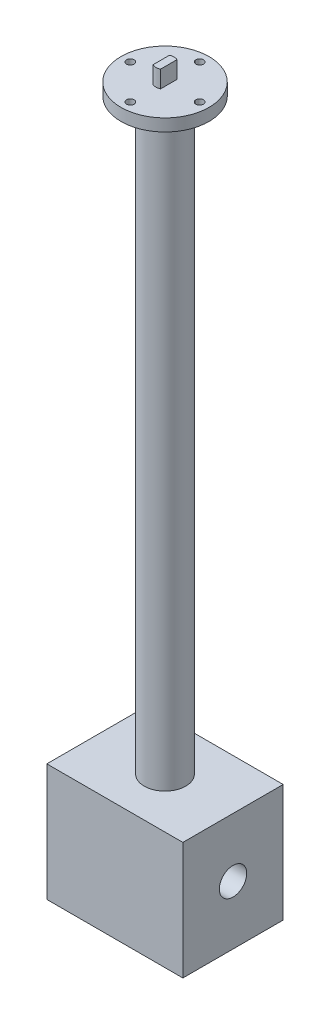
SolidWorks part; units mm, degrees
ref_plane "Front Plane" through (0, 0, 0) normal (0, 0, 1) x (1, 0, 0)
ref_plane "Top Plane" through (0, 0, 0) normal (0, 1, 0) x (1, 0, 0)
ref_plane "Right Plane" through (0, 0, 0) normal (1, 0, 0) x (0, 0, -1)
sketch "Sketch1" plane through (0, 0, 0) normal (0, 1, 0) x (1, 0, 0)
  circle A0 centre (0, 0) radius 22.86
  dimension "D1" = 45.72
extrude "Boss-Extrude1" add sketch "Sketch1" along normal blind 6.35
sketch "Sketch2" plane through (0, 6.35, 0) normal (0, 1, 0) x (1, 0, 0)
  line L0 (1.9685, 4.2668) -> (1.9685, -4.2668)
  line L1 (-1.9685, 4.2668) -> (-1.9685, -4.2668)
  line L2 (0, 0) -> (1.9685, 0) construction
  line L3 (0, 0) -> (-1.9685, 0) construction
  circle A0 centre (0, 0) radius 4.699
  dimension "D1" = 9.398
  dimension "D2" = 1.9685
  dimension "D3" = 1.9685
extrude "Boss-Extrude2" add sketch "Sketch2" along normal blind 8.89 contours L0 A0 L1 region at (0, 6.35, 0)
sketch "Sketch3" plane through (0, 0, 0) normal (0, -1, 0) x (1, 0, 0)
  circle A0 centre (0, 0) radius 10.795
  dimension "D1" = 21.59
extrude "Boss-Extrude3" add sketch "Sketch3" along normal blind 304.8
chamfer "Chamfer1" distance 3.81 angle 45 1 edges at (0, 0, -10.795)
sketch "Sketch4" plane through (0, 6.35, 0) normal (0, 1, 0) x (1, 0, 0)
  line L0 (0, 0) -> (0, 18) construction
  circle A0 centre (0, 0) radius 18 construction
  dimension "D1" = 36
hole_wizard "5/32 (0.15625) Diameter Hole1" positions "Sketch5" profile "Sketch6" hole size "5/32" standard "ANSI Inch" end condition up to next
sketch "Sketch5" plane through (0, 6.35, 0) normal (0, 1, 0) x (1, 0, 0)
  point P0 (0, 18)
sketch "Sketch6" plane through (0, 6.35, -18) normal (1, 0, 0) x (0, 0, 1)
  line L0 (0, 0) -> (0, 6.351)
  line L1 (0, 6.351) -> (1.9844, 6.351)
  line L2 (1.9844, 6.351) -> (1.9844, 0)
  line L5 (1.9844, 0) -> (0, 0)
  line L11 (0, -6.35) -> (0, 107.95) construction
  dimension "Thru Hole Dia." = 3.9688
  dimension "Thru Hole Depth" = 6.351
pattern_circular "CirPattern1" count 4 over 360 about axis through (0, 6.35, 0) along (0, 1, 0) of "5/32 (0.15625) Diameter Hole1"
sketch "Sketch7" plane through (0, -304.8, 0) normal (0, -1, 0) x (1, 0, 0)
  line L0 (-35.306, 26.035) -> (35.306, -26.035) construction
  line L1 (-35.306, 26.035) -> (35.306, 26.035)
  line L2 (-35.306, 26.035) -> (-35.306, -26.035)
  line L3 (-35.306, -26.035) -> (35.306, -26.035)
  line L4 (35.306, 26.035) -> (35.306, -26.035)
  point P4 (0, 0)
  dimension "D1" = 52.07
  dimension "D2" = 70.612
extrude "Boss-Extrude4" add sketch "Sketch7" along normal blind 60.96
sketch "Sketch8" plane through (35.306, 0, 0) normal (1, 0, 0) x (0, 0, -1)
  line L0 (-26.035, -304.8) -> (26.035, -365.76) construction
  circle A0 centre (0, -335.28) radius 7.112
  dimension "D1" = 14.224
extrude "Cut-Extrude1" cut sketch "Sketch8" against normal through all
sketch "Sketch9" plane through (0, 0, 0) normal (0, 0, 1) x (1, 0, 0)
  line L0 (-13.97, 7.62) -> (15.3255, 7.62)
  line L1 (15.3255, 7.62) -> (46.9483, 40.64)
  line L2 (46.9483, 40.64) -> (150.114, 40.64)
  line L3 (150.114, 40.64) -> (150.114, 43.815)
  line L4 (150.114, 43.815) -> (45.5927, 43.815)
  line L5 (45.5927, 43.815) -> (13.97, 10.795)
  line L6 (13.97, 10.795) -> (-13.97, 10.795)
  line L7 (-13.97, 10.795) -> (-13.97, 7.62)
  line L8 (-1.9685, 10.795) -> (1.9685, 10.795) construction
  line L9 (-1.9685, 15.24) -> (-1.9685, 6.35) construction
  line L10 (1.9685, 15.24) -> (1.9685, 6.35) construction
  point P14 (0, 10.795)
  point P15 (0, 10.795)
  dimension "D1" = 33.02
  dimension "D2" = 3.175
  dimension "D3" = 3.175
  dimension "D4" = 3.175
  dimension "D5" = 150.114
  dimension "D6" = 45.72
  dimension "D7" = 27.94
extrude "Boss-Extrude5" [suppressed] add sketch "Sketch9" along normal mid plane 22.86
fillet "Fillet1" [suppressed] radius 6.35
equation "\"D2@Sketch2\"=(.37-.215)/2"
